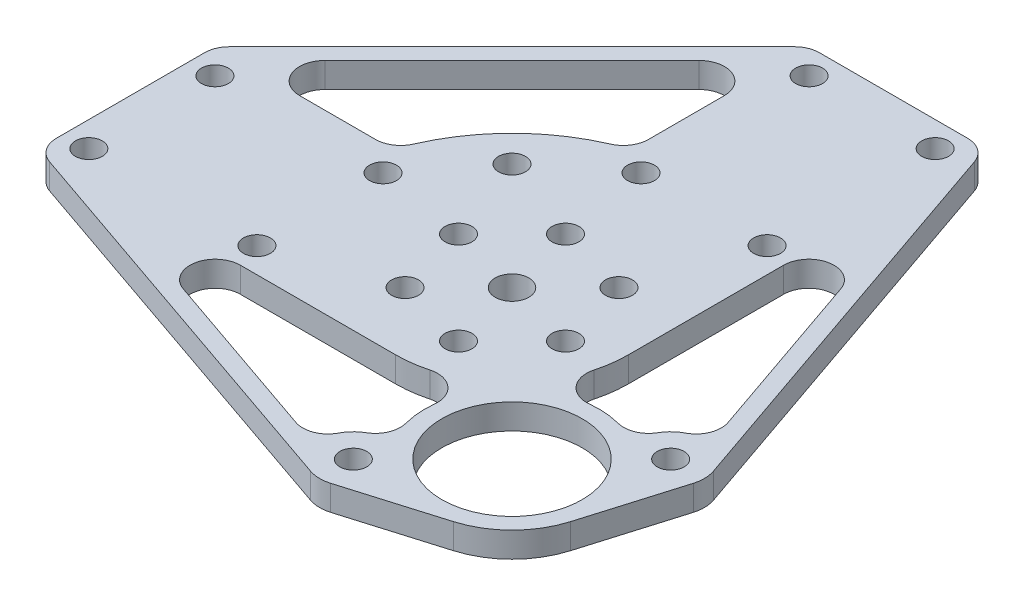
SolidWorks part; units mm, degrees
material "6061-T6 (SS)"
ref_plane "Front Plane" through (0, 0, 0) normal (0, 0, 1) x (1, 0, 0)
ref_plane "Top Plane" through (0, 0, 0) normal (0, 1, 0) x (1, 0, 0)
ref_plane "Right Plane" through (0, 0, 0) normal (1, 0, 0) x (0, 0, -1)
sketch "Sketch1" plane through (0, 0, 0) normal (0, 1, 0) x (1, 0, 0)
  line L0 (-14.5, -32) -> (14.5, -32) construction
  line L1 (10.85, 19.5) -> (-4.15, 19.5)
  line L2 (10.85, 19.5) -> (10.85, 39.5)
  line L3 (10.85, 39.5) -> (-4.15, 39.5)
  line L4 (-4.15, 19.5) -> (-4.15, 39.5)
  line L5 (10.85, 19.5) -> (-4.15, 39.5) construction
  line L6 (10.85, 39.5) -> (-4.15, 19.5) construction
  line L7 (-19.5, -10.85) -> (-39.5, -10.85)
  line L8 (-19.5, -10.85) -> (-19.5, 4.15)
  line L9 (-19.5, 4.15) -> (-39.5, 4.15)
  line L10 (-39.5, -10.85) -> (-39.5, 4.15)
  line L11 (-19.5, -10.85) -> (-39.5, 4.15) construction
  line L12 (-19.5, 4.15) -> (-39.5, -10.85) construction
  line L13 (20.7, 16) -> (-14, 16)
  line L14 (20.7, 16) -> (20.7, 43)
  line L15 (20.7, 43) -> (-14, 43)
  line L16 (-14, 16) -> (-14, 43)
  line L17 (20.7, 16) -> (-14, 43) construction
  line L18 (20.7, 43) -> (-14, 16) construction
  line L19 (-16, -20.7) -> (-43, -20.7)
  line L20 (-16, -20.7) -> (-16, 14)
  line L21 (-16, 14) -> (-43, 14)
  line L22 (-43, -20.7) -> (-43, 14)
  line L23 (-16, -20.7) -> (-43, 14) construction
  line L24 (-16, 14) -> (-43, -20.7) construction
  line L25 (10, -37) -> (-10, -37)
  line L26 (10, -37) -> (10, -27)
  line L27 (10, -27) -> (-10, -27)
  line L28 (-10, -37) -> (-10, -27)
  line L29 (10, -37) -> (-10, -27) construction
  line L30 (10, -27) -> (-10, -37) construction
  line L31 (37, -10) -> (27, -10)
  line L32 (37, -10) -> (37, 10)
  line L33 (37, 10) -> (27, 10)
  line L34 (27, -10) -> (27, 10)
  line L35 (37, -10) -> (27, 10) construction
  line L36 (37, 10) -> (27, -10) construction
  line L37 (32, 14.5) -> (32, -14.5) construction
  circle A0 centre (0, 0) radius 2
  circle A1 centre (0, 0) radius 9
  circle A2 centre (0, 0) radius 12.7
  point P3 (3.35, 29.5)
  point P8 (-29.5, -3.35)
  point P15 (0, -32)
  point P16 (-29.5, -3.35)
  point P17 (3.35, 29.5)
  point P30 (32, 0)
  point P38 (0, -32)
  point P41 (32, 0)
  dimension "D1" = 4
  dimension "D4" = 18
  dimension "D11" = 25.4
  dimension "D2" = 20
  dimension "D3" = 15
  dimension "D5" = 34.7
  dimension "D6" = 27
  dimension "D7" = 2
  dimension "D8" = 2
  dimension "D9" = 16
  dimension "D10" = 16
  dimension "D12" = 32
  dimension "D13" = 10
  dimension "D14" = 20
  dimension "D15" = 32
  dimension "D16" = 4.5
sketch "Sketch2" plane through (0, 0, 0) normal (0, 1, 0) x (1, 0, 0)
  line L3 (-16.5, -13.85) -> (-42.5, -13.85)
  line L4 (-42.5, -13.85) -> (-42.5, 7.15)
  line L5 (-42.5, 7.15) -> (-24.825, 24.825)
  line L6 (-19.5, -10.85) -> (-39.5, -10.85) construction
  line L9 (-39.5, -10.85) -> (-39.5, 4.15) construction
  line L10 (-19.5, -10.85) -> (-19.5, 4.15) construction
  line L12 (-19.5, 4.15) -> (-39.5, 4.15) construction
  line L16 (-16.5, -13.85) -> (-16.5, -29.1277)
  line L22 (16.9749, -34.4749) -> (25.7249, -25.7249)
  line L29 (25.7249, -25.7249) -> (-24.825, 24.825)
  line L39 (12, -27) -> (12, -39)
  line L40 (12, -39) -> (-12, -39)
  line L41 (-12, -39) -> (-12, -27)
  line L42 (12, -34.4495) -> (12, -39)
  line L43 (12, -39) -> (-12, -39)
  line L44 (-12, -39) -> (-12, -34.4495)
  arc A0 (-16.5, -29.1277) -> (-12, -34.4495) centre (-14.5, -32) ccw
  arc A2 (12, -34.4495) -> (16.9749, -34.4749) centre (14.5, -32) ccw
  dimension "D1" = 7
  dimension "D2" = 3
  dimension "D3" = 45
  dimension "D4" = 2
  dimension "D5" = 3
  dimension "D6" = 3
  dimension "D8" = 3
extrude "Boss-Extrude1" add sketch "Sketch2" along normal blind 3
mirror "Mirror5" about plane through (25.7249, 3, 25.7249) normal (-0.7071, 0, 0.7071) of bodies 101
hole_wizard "M3 Clearance Hole1" positions "Sketch3" profile "Sketch4" hole size "M3" standard "ANSI Metric" end condition up to next
sketch "Sketch3" plane through (0, 3, 0) normal (0, 1, 0) x (1, 0, 0)
  point P0 (-39.5, 4.15)
  point P3 (-19.5, 4.15)
  point P6 (-19.5, -10.85)
  point P9 (-39.5, -10.85)
  point P12 (-4.15, 19.5)
  point P15 (-4.15, 39.5)
  point P18 (10.85, 39.5)
  point P21 (10.85, 19.5)
sketch "Sketch4" plane through (-39.5, 3, -4.15) normal (1, 0, 0) x (0, 0, 1)
  line L0 (0, 0) -> (0, 3)
  line L1 (0, 3) -> (1.6, 3)
  line L2 (1.6, 3) -> (1.6, 0)
  line L5 (1.6, 0) -> (0, 0)
  line L11 (0, -6.35) -> (0, 107.95) construction
  dimension "Thru Hole Dia." = 3.2
  dimension "Thru Hole Depth" = 3
hole_wizard "M3 Clearance Hole2" positions "Sketch5" profile "Sketch6" hole size "M3" standard "ANSI Metric" end condition up to next
sketch "Sketch5" plane through (0, 3, 0) normal (0, 1, 0) x (1, 0, 0)
  line L4 (-8.6933, 2.3294) -> (-2.3294, 8.6933) construction
  line L5 (0, 0) -> (-5.5114, 5.5114) construction
  line L7 (-1000, 0) -> (49000, 0) construction
  circle A0 centre (0, 0) radius 9 construction
  point P23 (-2.3294, 8.6933)
  point P46 (6.364, 6.364)
  point P47 (8.6933, -2.3294)
  point P48 (2.3294, -8.6933)
  point P49 (-6.364, -6.364)
  point P50 (-8.6933, 2.3294)
  dimension "D1" = 45
  dimension "D2" = 6
sketch "Sketch6" plane through (-2.3294, 3, -8.6933) normal (1, 0, 0) x (0, 0, 1)
  line L0 (0, 0) -> (0, 3)
  line L1 (0, 3) -> (1.6, 3)
  line L2 (1.6, 3) -> (1.6, 0)
  line L5 (1.6, 0) -> (0, 0)
  line L11 (0, -6.35) -> (0, 107.95) construction
  dimension "Thru Hole Dia." = 3.2
  dimension "Thru Hole Depth" = 3
hole_wizard "Ø4.0 (4) Diameter Hole1" positions "Sketch7" profile "Sketch8" hole size "Ø4.0" standard "ANSI Metric" end condition up to next
sketch "Sketch7" plane through (0, 3, 0) normal (0, 1, 0) x (1, 0, 0)
  point P0 (0, 0)
sketch "Sketch8" plane through (0, 3, 0) normal (1, 0, 0) x (0, 0, 1)
  line L0 (0, 0) -> (0, 3)
  line L1 (0, 3) -> (2, 3)
  line L2 (2, 3) -> (2, 0)
  line L5 (2, 0) -> (0, 0)
  line L11 (0, -6.35) -> (0, 107.95) construction
  dimension "Thru Hole Dia." = 4
  dimension "Thru Hole Depth" = 3
sketch "Sketch13" plane through (0, 3, 0) normal (0, 1, 0) x (1, 0, 0)
  line L0 (-39.6716, 7.15) -> (-21.3337, 7.15)
  line L1 (0, 0) -> (-24.825, 24.825) construction
  line L2 (-7.15, 42.5) -> (-42.5, 7.15) construction
  line L4 (-23.4108, 23.4108) -> (-15.9099, 15.9099)
  line L5 (-5.7358, 41.0858) -> (-41.0858, 5.7358)
  line L6 (-23.4108, 23.4108) -> (-39.6716, 7.15)
  circle A2 centre (0, 0) radius 22.5 construction
  circle A3 centre (-19.5, 4.15) radius 1.6 construction
  arc A4 (-21.3337, 7.15) -> (-15.9099, 15.9099) centre (0, 0) cw
  dimension "D1" = 45
  dimension "D2" = 3
  dimension "D3" = 2
extrude "Cut-Extrude3" cut sketch "Sketch13" against normal up to surface (3 mm away) contours L0 A4 L4 L6 region at (-26.206, 3, -13.3731) up to face at (0, 0, 2)
mirror "Mirror6" about plane through (0, -28.7929, 0) normal (-0.7071, 0, 0.7071) of "Cut-Extrude3"
fillet "Fillet5" radius 3 4 edges at (-7.15, 1.5, -39.6716) (-7.15, 1.5, -21.3337) (-21.3337, 1.5, -7.15) (-39.6716, 1.5, -7.15)
hole_wizard "M3 Clearance Hole3" positions "Sketch14" profile "Sketch15" hole size "M3" standard "ANSI Metric" end condition up to next
sketch "Sketch14" plane through (0, 3, 0) normal (0, 1, 0) x (1, 0, 0)
  line L0 (-12.7279, 12.7279) -> (0, 0) construction
  line L2 (-12.2713, 34.5503) -> (-34.5503, 12.2713) construction
  circle A2 centre (-12.7279, 12.7279) radius 3
  point P0 (-12.7279, 12.7279)
  dimension "D1" = 6
  dimension "D2" = 18
sketch "Sketch15" plane through (-12.7279, 3, -12.7279) normal (1, 0, 0) x (0, 0, 1)
  line L0 (0, 0) -> (0, 3)
  line L1 (0, 3) -> (1.6, 3)
  line L2 (1.6, 3) -> (1.6, 0)
  line L5 (1.6, 0) -> (0, 0)
  line L11 (0, -6.35) -> (0, 107.95) construction
  dimension "Thru Hole Dia." = 3.2
  dimension "Thru Hole Depth" = 3
sketch "Sketch16" plane through (0, 3, 0) normal (0, 1, 0) x (1, 0, 0)
  line L0 (-16.5, -13.85) -> (-10.4933, -8.808)
  line L1 (13.85, 16.5) -> (8.808, 10.4933)
  line L16 (16.9749, -34.4749) -> (34.4749, -16.9749)
  line L17 (34.4495, -12) -> (39, -12)
  line L18 (39, -12) -> (39, 12)
  line L19 (39, 12) -> (34.4495, 12)
  line L20 (29.1277, 16.5) -> (13.85, 16.5)
  line L21 (13.85, 16.5) -> (13.85, 42.5)
  line L22 (13.85, 42.5) -> (-7.15, 42.5)
  line L23 (-7.15, 42.5) -> (-42.5, 7.15)
  line L24 (-42.5, 7.15) -> (-42.5, -13.85)
  line L25 (-42.5, -13.85) -> (-16.5, -13.85)
  line L26 (-16.5, -13.85) -> (-16.5, -29.1277)
  line L27 (-12, -34.4495) -> (-12, -39)
  line L28 (-12, -39) -> (12, -39)
  line L29 (12, -39) -> (12, -34.4495)
  line L30 (16.9749, -34.4749) -> (34.4749, -16.9749)
  line L31 (34.4495, -12) -> (39, -12)
  line L32 (39, -12) -> (39, 12)
  line L33 (39, 12) -> (34.4495, 12)
  line L34 (29.1277, 16.5) -> (13.85, 16.5)
  line L40 (-16.5, -13.85) -> (-16.5, -29.1277)
  line L41 (-12, -34.4495) -> (-12, -39)
  line L42 (-12, -39) -> (12, -39)
  line L43 (12, -39) -> (12, -34.4495)
  arc A0 (-10.4933, -8.808) -> (8.808, 10.4933) centre (0, 0) ccw
  arc A5 (34.4749, -16.9749) -> (34.4495, -12) centre (32, -14.5) ccw
  arc A6 (34.4495, 12) -> (29.1277, 16.5) centre (32, 14.5) ccw
  arc A7 (-16.5, -29.1277) -> (-12, -34.4495) centre (-14.5, -32) ccw
  arc A8 (12, -34.4495) -> (16.9749, -34.4749) centre (14.5, -32) ccw
  arc A9 (34.4749, -16.9749) -> (34.4495, -12) centre (32, -14.5) ccw
  arc A10 (34.4495, 12) -> (29.1277, 16.5) centre (32, 14.5) ccw
  arc A11 (-16.5, -29.1277) -> (-12, -34.4495) centre (-14.5, -32) ccw
  arc A12 (12, -34.4495) -> (16.9749, -34.4749) centre (14.5, -32) ccw
  dimension "D1" = 27.4
  dimension "D2" = 0
extrude "Cut-Extrude4" cut sketch "Sketch16" against normal up to surface (3 mm away) up to face at (-12.7279, 0, -11.1279)
sketch "Sketch17" plane through (0, 3, 0) normal (0, 1, 0) x (1, 0, 0)
  line L0 (0, 0) -> (17.6777, -17.6777) construction
  line L1 (-12.2713, 34.5503) -> (-34.5503, 12.2713) construction
  line L2 (-16.5, -13.85) -> (13.4837, -27.1399)
  line L3 (13.85, 16.5) -> (8.808, 10.4933) construction
  line L4 (-10.4933, -8.808) -> (-16.5, -13.85) construction
  line L5 (13.85, 16.5) -> (8.808, 10.4933)
  line L6 (-10.4933, -8.808) -> (-16.5, -13.85)
  line L7 (13.85, 16.5) -> (27.1399, -13.4837)
  arc A0 (13.4837, -27.1399) -> (27.1399, -13.4837) centre (17.6777, -17.6777) ccw
  circle A1 centre (17.6777, -17.6777) radius 8.35
  arc A2 (-10.4933, -8.808) -> (8.808, 10.4933) centre (0, 0) ccw construction
  arc A3 (-10.4933, -8.808) -> (8.808, 10.4933) centre (0, 0) ccw
  dimension "D1" = 2
  dimension "D2" = 20.7
  dimension "D3" = 25
extrude "Boss-Extrude2" add sketch "Sketch17" against normal up to surface (3 mm away) up to face at (-12.7279, 0, -11.1279)
sketch "Sketch18" plane through (0, 3, 0) normal (0, 1, 0) x (1, 0, 0)
  line L0 (8.2378, -27.1175) -> (27.1175, -8.2378) construction
  line L1 (-7.15, 42.5) -> (-42.5, 7.15) construction
  line L2 (30.899, -6.9336) -> (13.85, 42.5)
  line L3 (27.5964, -20.6342) -> (30.9509, -9.3804)
  line L4 (27.1399, -13.4837) -> (13.85, 16.5) construction
  line L5 (13.85, 42.5) -> (13.85, 16.5) construction
  line L6 (27.1399, -13.4837) -> (13.85, 16.5)
  line L7 (13.85, 42.5) -> (13.85, 16.5)
  line L8 (17.6777, -17.6777) -> (0, 0) construction
  line L9 (-42.5, -13.85) -> (-16.5, -13.85)
  line L10 (13.4837, -27.1399) -> (-16.5, -13.85)
  line L11 (20.6342, -27.5964) -> (9.3804, -30.9509)
  line L12 (6.9336, -30.899) -> (-42.5, -13.85)
  arc A0 (30.9509, -9.3804) -> (30.899, -6.9336) centre (27.1175, -8.2378) ccw
  arc A2 (13.4837, -27.1399) -> (27.1399, -13.4837) centre (17.6777, -17.6777) ccw construction
  arc A3 (27.5964, -20.6342) -> (27.1399, -13.4837) centre (17.6777, -17.6777) ccw
  arc A4 (20.6342, -27.5964) -> (13.4837, -27.1399) centre (17.6777, -17.6777) cw
  arc A5 (9.3804, -30.9509) -> (6.9336, -30.899) centre (8.2378, -27.1175) cw
  point P5 (17.6777, -17.6777)
  dimension "D2" = 8
  dimension "D1" = 13.35
extrude "Boss-Extrude3" add sketch "Sketch18" against normal up to surface (3 mm away) up to face at (-12.7279, 0, -11.1279)
hole_wizard "M3 Clearance Hole4" positions "Sketch19" profile "Sketch20" hole size "M3" standard "ANSI Metric" end condition up to next
sketch "Sketch19" plane through (0, 3, 0) normal (0, 1, 0) x (1, 0, 0)
  point P0 (8.2378, -27.1175)
  point P3 (27.1175, -8.2378)
sketch "Sketch20" plane through (8.2378, 3, 27.1175) normal (1, 0, 0) x (0, 0, 1)
  line L0 (0, 0) -> (0, 3)
  line L1 (0, 3) -> (1.6, 3)
  line L2 (1.6, 3) -> (1.6, 0)
  line L5 (1.6, 0) -> (0, 0)
  line L11 (0, -6.35) -> (0, 107.95) construction
  dimension "Thru Hole Dia." = 3.2
  dimension "Thru Hole Depth" = 3
sketch "Sketch21" plane through (0, 3, 0) normal (0, 1, 0) x (1, 0, 0)
  line L0 (13.85, 42.5) -> (13.85, 0) construction
  line L1 (0, 0) -> (24.9962, -24.9962) construction
  line L2 (13.85, 36.3658) -> (27.8788, -4.3109)
  line L3 (30.899, -6.9336) -> (13.85, 42.5) construction
  line L4 (11.9113, -9.0828) -> (11.105, -8.2766)
  line L5 (13.85, 0) -> (13.85, 36.3658)
  line L6 (0, -13.85) -> (-36.3658, -13.85)
  line L7 (9.0828, -11.9113) -> (8.2766, -11.105)
  line L8 (-36.3658, -13.85) -> (4.3109, -27.8788)
  arc A0 (11.105, -8.2766) -> (13.85, 0) centre (0, 0) ccw
  arc A1 (20.6342, -27.5964) -> (27.5964, -20.6342) centre (17.6777, -17.6777) ccw construction
  arc A2 (27.8788, -4.3109) -> (23.6465, -6.2498) centre (27.1175, -8.2378) ccw
  arc A3 (20.2869, -7.662) -> (23.6465, -6.2498) centre (21.0432, -4.7589) ccw
  arc A4 (7.662, -20.2869) -> (9.0828, -11.9113) centre (17.6777, -17.6777) cw
  circle A5 centre (17.6777, -17.6777) radius 10.35
  arc A6 (20.2869, -7.662) -> (11.9113, -9.0828) centre (17.6777, -17.6777) ccw
  arc A7 (7.662, -20.2869) -> (6.2498, -23.6465) centre (4.7589, -21.0432) cw
  arc A8 (4.3109, -27.8788) -> (6.2498, -23.6465) centre (8.2378, -27.1175) cw
  arc A9 (8.2766, -11.105) -> (0, -13.85) centre (0, 0) cw
  point P16 (25.2682, -5.6332)
  dimension "D1" = 8
  dimension "D5" = 3
  dimension "D2" = 2
  dimension "D4" = 2
  dimension "D3" = 2
extrude "Cut-Extrude5" cut sketch "Sketch21" against normal up to surface (3 mm away) up to face at (8.2378, 0, 28.7175)
fillet "Fillet6" radius 3 6 edges at (13.85, 1.5, -36.3658) (27.8788, 1.5, 4.3109) (11.105, 1.5, 8.2766) (-36.3658, 1.5, 13.85) (8.2766, 1.5, 11.105) (4.3109, 1.5, 27.8788)
fillet "Fillet7" radius 3 6 edges at (11.9113, 1.5, 9.0828) (9.0828, 1.5, 11.9113) (-42.5, 1.5, -7.15) (-7.15, 1.5, -42.5) (13.85, 1.5, -42.5) (-42.5, 1.5, 13.85)
